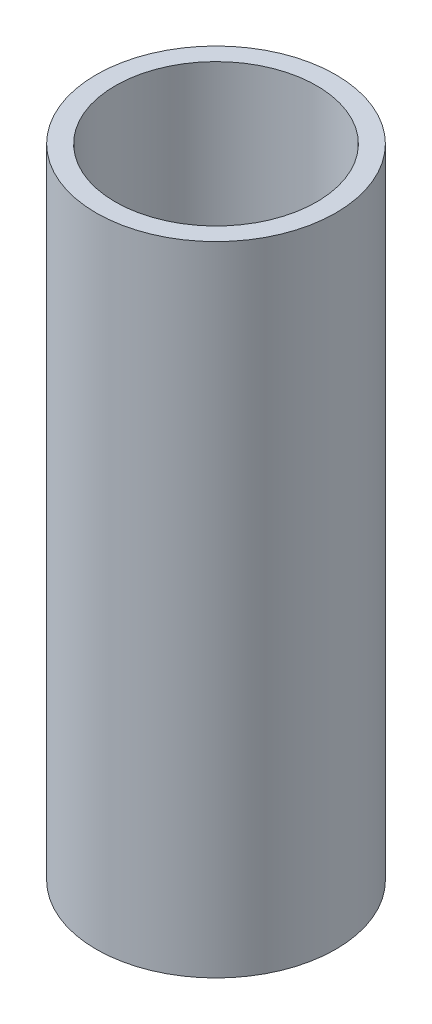
SolidWorks part; units mm, degrees
ref_plane "Front Plane" through (0, 0, 0) normal (0, 0, 1) x (1, 0, 0)
ref_plane "Top Plane" through (0, 0, 0) normal (0, 1, 0) x (1, 0, 0)
ref_plane "Right Plane" through (0, 0, 0) normal (1, 0, 0) x (0, 0, -1)
sketch "Sketch1" plane through (0, 0, 0) normal (0, 1, 0) x (1, 0, 0)
  circle A0 centre (0, 0) radius 25
  dimension "SLEEVE_OD" = 50
extrude "Boss-Extrude1" add sketch "Sketch1" along normal blind 133.0915
sketch "Sketch2" plane through (0, 0, 0) normal (0, 1, 0) x (1, 0, 0)
  circle A0 centre (0, 0) radius 21.0171
  dimension "BORE_D" = 42.0343
extrude "Cut-Extrude1" cut sketch "Sketch2" along normal through all
chamfer "Chamfer1" distance 2.4588 angle 45 rebuild error yes
